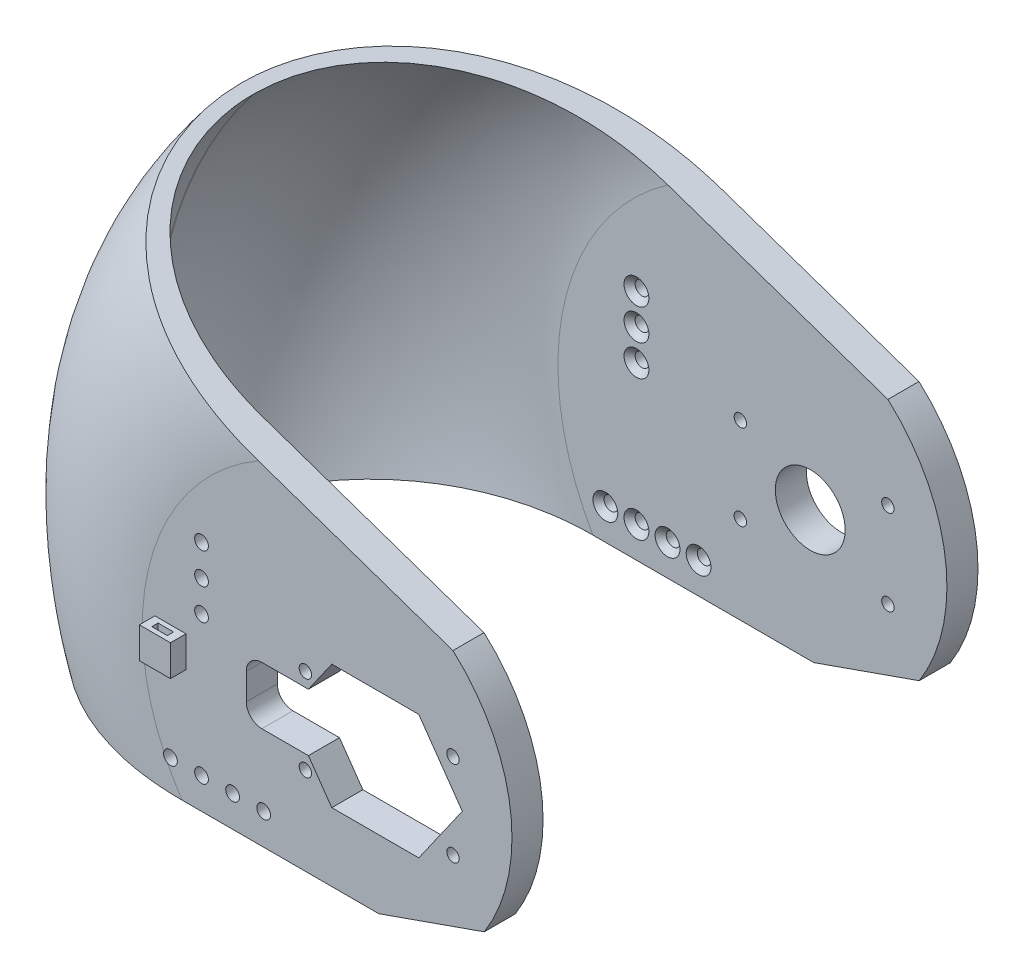
SolidWorks part; units mm, degrees
ref_plane "Front Plane" through (0, 0, 0) normal (0, 0, 1) x (1, 0, 0)
ref_plane "Top Plane" through (0, 0, 0) normal (0, 1, 0) x (1, 0, 0)
ref_plane "Right Plane" through (0, 0, 0) normal (1, 0, 0) x (0, 0, -1)
sketch "Sketch1" plane through (0, 0, 0) normal (0, 0, 1) x (1, 0, 0)
  line L0 (1.4338, -53.34) -> (-182.88, -53.34)
  line L2 (-149.9122, 117.5439) -> (31.75, 54.9926)
  line L3 (31.75, 54.9926) -> (0, 0) construction
  line L4 (0, 0) -> (86.4977, 0) construction
  line L6 (-28.575, -17.4625) -> (-28.575, 17.4625) construction
  line L7 (-28.575, -17.4625) -> (31.75, -17.4625) construction
  line L8 (31.75, -17.4625) -> (31.75, 17.4625) construction
  line L9 (-28.575, 17.4625) -> (31.75, 17.4625) construction
  line L10 (1.4338, -53.34) -> (44.5517, -38.1921)
  circle A0 centre (0, 0) radius 50.8 construction
  circle A1 centre (0, 0) radius 14.2875
  arc A4 (-149.9122, 117.5439) -> (-182.88, -53.34) centre (0, 0) ccw
  arc A10 (31.75, 54.9926) -> (44.5517, -38.1921) centre (-16.9805, 0.8263) cw
  circle A11 centre (-28.575, -17.4625) radius 2.54
  circle A12 centre (-28.575, 17.4625) radius 2.54
  circle A13 centre (31.75, 17.4625) radius 2.54
  circle A14 centre (31.75, -17.4625) radius 2.54
  circle A15 centre (-106.68, -40.64) radius 2.3813 construction
  circle A16 centre (-93.98, -40.64) radius 2.3813 construction
  circle A17 centre (-81.28, -40.64) radius 2.3813 construction
  circle A18 centre (-68.58, -40.64) radius 2.3813 construction
  circle A23 centre (-93.98, 41.91) radius 2.3813 construction
  circle A24 centre (-93.98, 29.21) radius 2.3813 construction
  circle A25 centre (-93.98, 16.51) radius 2.3813 construction
  point P32 (-187.0508, 36.0868)
  point P42 (-28.575, 0)
  dimension "D1" = 101.6
  dimension "D2" = 28.575
  dimension "D9" = 63.5
  dimension "D10" = 76.2
  dimension "D11" = 4
  dimension "D13" = 190.5
  dimension "D3" = 19
  dimension "D6" = 53.34
  dimension "D4" = 4.7625
  dimension "D5" = 12.7
  dimension "D7" = 72.8605
  dimension "D16" = 5.08
  dimension "D17" = 4.7625
  dimension "D22" = 43.118
  dimension "D8" = 60
  dimension "D12" = 12.7
  dimension "D14" = 60.325
  dimension "D15" = 34.925
  dimension "D18" = 12.7
  dimension "D19" = 12.7
  dimension "D20" = 57.15
  dimension "D21" = 31.75
  dimension "D23" = 15.1479
extrude "Boss-Extrude1" add sketch "Sketch1" against normal blind 190.5
sketch "Sketch2" plane through (0, -53.34, 0) normal (0, -1, 0) x (1, 0, 0)
  line L0 (-190.5, 0) -> (-190.5, -190.5) construction
  line L1 (-190.5, -12.7) -> (55.88, -12.7)
  line L2 (-190.5, -12.7) -> (-190.5, -177.8)
  line L3 (-190.5, -177.8) -> (55.88, -177.8)
  line L6 (-182.88, 0) -> (1.4338, 0) construction
  line L7 (55.88, -190.5) -> (55.88, 0) construction
  line L8 (55.88, -12.7) -> (55.88, -177.8)
  line L9 (-190.5, 0) -> (-190.5, -190.5) construction
  dimension "D1" = 165.1
  dimension "D2" = 12.7
extrude "Cut-Extrude1" cut sketch "Sketch2" against normal through all
sketch "Sketch3" plane through (0, 0, -177.8) normal (0, 0, 1) x (1, 0, 0)
  line L0 (-149.9122, 117.5439) -> (-145.109, 115.89)
  line L2 (-182.88, -53.34) -> (-177.8, -53.34)
  line L3 (-182.88, -53.34) -> (1.4338, -53.34) construction
  arc A0 (-182.88, -53.34) -> (-149.9122, 117.5439) centre (0, 0) cw
  arc A1 (-149.9122, 117.5439) -> (-182.88, -53.34) centre (0, 0) ccw construction
  arc A2 (-177.8, -53.34) -> (-145.109, 115.89) centre (2.1551, -0.3303) cw
  point P14 (-187.0508, 36.0868)
  point P15 (-182.0399, 35.2516)
  dimension "D1" = 5.08
  dimension "D2" = 5.08
  dimension "D3" = 5.08
  dimension "D4" = 19
extrude "Boss-Extrude2" add sketch "Sketch3" along normal up to next (165.1 mm away)
sketch "Sketch5" plane through (0, 0, 0) normal (0, 0, 1) x (1, 0, 0)
  line L0 (-17.78, -25.4) -> (17.78, -25.4)
  line L1 (17.78, 25.4) -> (-17.78, 25.4)
  line L2 (17.78, -25.4) -> (35.5653, 0)
  line L4 (35.5653, 0) -> (17.78, 25.4)
  line L5 (-17.78, 25.4) -> (-27.3396, 11.7475)
  line L7 (-27.3396, -11.7475) -> (-17.78, -25.4)
  line L8 (-27.3396, -11.7475) -> (-46.3896, -11.7475)
  line L9 (-52.7396, -5.3975) -> (-52.7396, 5.3975)
  line L10 (-46.3896, 11.7475) -> (-27.3396, 11.7475)
  arc A0 (-46.3896, -11.7475) -> (-52.7396, -5.3975) centre (-46.3896, -5.3975) cw
  arc A1 (-52.7396, 5.3975) -> (-46.3896, 11.7475) centre (-46.3896, 5.3975) cw
  point P9 (0, -25.4)
  point P16 (-52.7396, -11.7475)
  point P19 (-52.7396, 11.7475)
  dimension "D8" = 6.35
  dimension "D1" = 125
  dimension "D2" = 35.56
  dimension "D3" = 50.8
  dimension "D4" = 125
  dimension "D5" = 23.495
  dimension "D6" = 125
  dimension "D7" = 25.4
extrude "Cut-Extrude3" cut sketch "Sketch5" against normal up to next
fillet "Fillet2" radius 82.296 2 edges at (-182.0399, 35.2516, -12.7) (-182.0399, 35.2516, -177.8)
fillet "Fillet3" radius 95.25 2 edges at (-187.0508, 36.0868, -190.5) (-187.0508, 36.0868, 0)
sketch "Sketch6" plane through (0, 0, 0) normal (0, 0, 1) x (1, 0, 0)
  line L0 (-78.9139, -53.34) -> (1.4338, -53.34) construction
  circle A0 centre (-71.0424, 41.91) radius 2.3813 construction
  circle A1 centre (-71.0424, 29.21) radius 2.3813 construction
  circle A2 centre (-71.0424, 16.51) radius 2.3813 construction
  circle A5 centre (-71.0424, -40.64) radius 2.3813 construction
  circle A6 centre (-58.3424, -40.64) radius 2.3812 construction
  circle A7 centre (-45.6424, -40.64) radius 2.3812 construction
  circle A8 centre (-83.7424, -40.64) radius 2.3813 construction
  point P0 (-71.0424, 41.91)
  point P2 (-71.0424, 29.21)
  point P4 (-71.0424, 16.51)
  point P12 (-71.0424, -40.64)
  point P14 (-58.3424, -40.64)
  dimension "D3" = 4.7625
  dimension "D5" = 47.0761
  dimension "D6" = 4.7625
  dimension "D1" = 12.7
  dimension "D2" = 12.7
  dimension "D4" = 69.85
  dimension "D7" = 12.7
  dimension "D8" = 12.7
  dimension "D9" = 12.7
  dimension "D10" = 12.7
sketch "Sketch15" plane through (0, 0, -12.7) normal (0, 0, -1) x (-1, 0, 0)
  line L2 (-1.4338, -53.34) -> (88.8337, -53.34)
  line L3 (58.1967, 85.9637) -> (-31.75, 54.9926)
  line L4 (-1.4338, -53.34) -> (88.8337, -53.34)
  line L5 (58.1967, 85.9637) -> (-31.75, 54.9926)
  line L33 (-44.5517, -38.1921) -> (-1.4338, -53.34)
  line L34 (-44.5517, -38.1921) -> (-1.4338, -53.34)
  circle A0 centre (71.0424, 29.21) radius 2.3813 construction
  circle A1 centre (71.0424, 29.21) radius 2.3813 construction
  arc A2 (88.8337, -53.34) -> (58.1967, 85.9637) centre (-2.1551, -0.3303) ccw
  arc A3 (-31.75, 54.9926) -> (-44.5517, -38.1921) centre (16.9805, 0.8263) ccw
  arc A4 (88.8337, -53.34) -> (58.1967, 85.9637) centre (-2.1551, -0.3303) ccw
  arc A5 (-31.75, 54.9926) -> (-44.5517, -38.1921) centre (16.9805, 0.8263) ccw
  point P2 (71.0424, 29.21)
  point P23 (71.0424, 41.91)
  point P26 (71.0424, 16.51)
  point P37 (58.3424, -40.64)
  point P74 (71.0424, -40.64)
  point P180 (45.6424, -40.64)
  point P183 (83.7424, -40.64)
  dimension "D1" = 0
hole_wizard "CSK for #10 Flat Head Machine Screw (100)12" positions "Sketch15" profile "Sketch17" countersink size "#10" standard "ANSI Inch" end condition through all
sketch "Sketch17" plane through (-83.7424, -40.64, -12.7) normal (1, 0, 0) x (0, 1, 0)
  line L0 (0, 0) -> (0, 20.6846)
  line L1 (0, 20.6846) -> (2.8067, 20.6846)
  line L2 (2.8067, 20.6846) -> (2.8067, 2.2733)
  line L3 (2.8067, 2.2733) -> (5.08, 0)
  line L5 (5.08, 0) -> (0, 0)
  line L6 (-2.8067, 2.2733) -> (-5.08, 0) construction
  line L11 (0, -6.35) -> (0, 107.95) construction
  dimension "Thru Hole Dia." = 5.6134
  dimension "Thru Hole Depth" = 20.6846
  dimension "Near C'Sink Dia." = 10.16
  dimension "Near C'Sink Angle" = 90
ref_plane "Plane1" through (0, 0, -95.25) normal (0, 0, -1) x (-1, 0, 0)
mirror "Mirror1" about plane through (0, 0, -95.25) normal (0, 0, -1) of "CSK for #10 Flat Head Machine Screw (100)12"
ref_plane "Plane2" through (-187.0508, 0, 0) normal (1, 0, 0) x (0, 0, -1)
sketch "Sketch21" plane through (0, 0, 0) normal (0, 0, 1) x (1, 0, 0)
  line L1 (-90.0924, 6.35) -> (-77.3924, 6.35)
  line L2 (-90.0924, 6.35) -> (-90.0924, -6.35)
  line L3 (-90.0924, -6.35) -> (-77.3924, -6.35)
  line L4 (-77.3924, 6.35) -> (-77.3924, -6.35)
  point P4 (-83.7424, -6.35)
  point P6 (-77.3924, 0)
  dimension "D1" = 12.7
  dimension "D2" = 12.7
extrude "Boss-Extrude4" add sketch "Sketch21" along normal blind 6.35
sketch "Sketch22" plane through (-83.7424, 6.35, 0) normal (0, -1, 0) x (0, 0, 1)
  line L0 (6.35, 6.35) -> (0, 6.35) construction
  line L1 (1.905, 3.175) -> (4.445, 3.175)
  line L2 (1.905, 3.175) -> (1.905, -3.175)
  line L3 (1.905, -3.175) -> (4.445, -3.175)
  line L4 (4.445, 3.175) -> (4.445, -3.175)
  line L7 (6.35, 6.35) -> (6.35, -6.35) construction
  dimension "D1" = 2.54
  dimension "D2" = 6.35
  dimension "D3" = 3.175
  dimension "D4" = 1.905
extrude "Cut-Extrude6" cut sketch "Sketch22" along normal up to next
mirror "Mirror2" about plane through (0, 0, -95.25) normal (0, 0, -1) of "Cut-Extrude6", "Boss-Extrude4"
ref_plane "Plane3" through (-181.102, 0, 0) normal (1, 0, 0) x (0, 0, -1)
